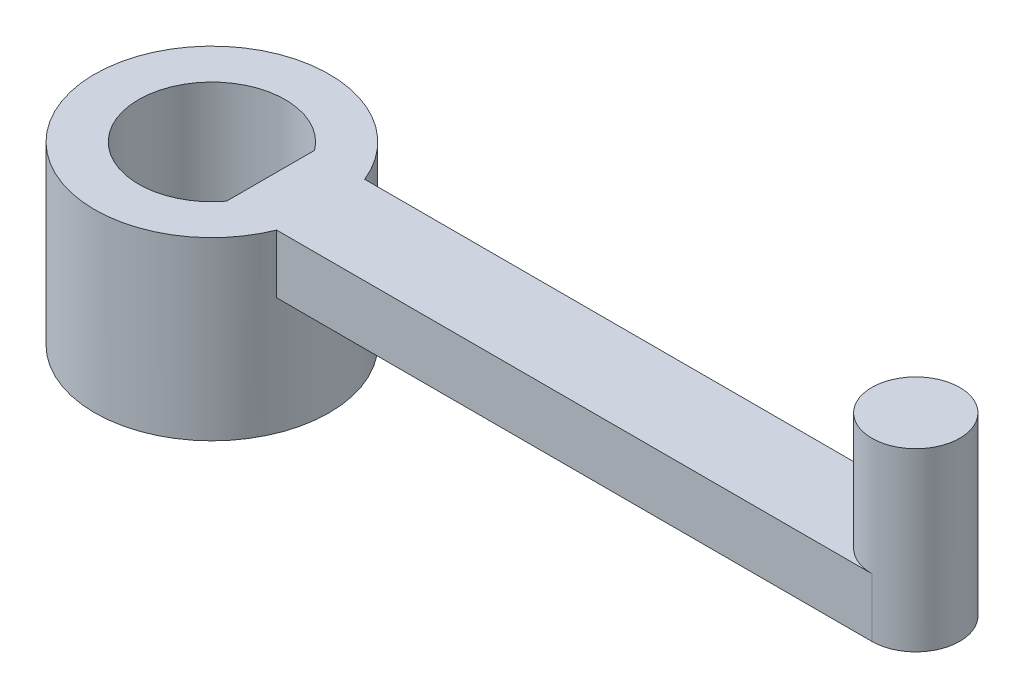
SolidWorks part; units mm, degrees
ref_plane "Front" through (0, 0, 0) normal (0, 0, 1) x (1, 0, 0)
ref_plane "Top" through (0, 0, 0) normal (0, 1, 0) x (1, 0, 0)
ref_plane "Right" through (0, 0, 0) normal (1, 0, 0) x (0, 0, -1)
sketch "Sketch1" plane through (0, 0, 0) normal (0, 1, 0) x (1, 0, 0)
  line L1 (6.35, 4.7625) -> (76.2, 4.7625)
  line L2 (6.35, 4.7625) -> (6.35, -4.7625)
  line L3 (6.35, -4.7625) -> (76.2, -4.7625)
  line L4 (76.2, 4.7625) -> (76.2, -4.7625)
  circle A0 centre (0, 0) radius 12.7
  circle A1 centre (0, 0) radius 7.9375
  circle A2 centre (76.2, 0) radius 4.7625
  dimension "D1" = 25.4
  dimension "D2" = 15.875
  dimension "D3" = 9.525
  dimension "D4" = 76.2
extrude "Boss-Extrude1" add sketch "Sketch1" against normal blind 6.35 contours A2 L1 A0 L3 | L4 A2 | L4 A2 region at (42.4364, 0, 0) region at (78.2213, 0, 0) region at (74.1787, 0, 0)
extrude "Boss-Extrude2" add sketch "Sketch1<3>" against normal blind 19.05 contours A1 L1 A0 L3 | A1 L3 A0 L1 | L2 A1 region at (-8.2902, 0, 0) region at (6.9908, 0, 0) region at (9.8994, 0, 0)
sketch "Sketch1<3>" plane through (0, 0, 0) normal (0, 1, 0) x (1, 0, 0) same geometry as "Sketch1"
extrude "Boss-Extrude3" add sketch "Sketch1<4>" along normal blind 12.7 contours L4 A2 | L4 A2 region at (78.2213, 0, 0) region at (74.1787, 0, 0)
sketch "Sketch1<4>" plane through (0, 0, 0) normal (0, 1, 0) x (1, 0, 0) same geometry as "Sketch1"
